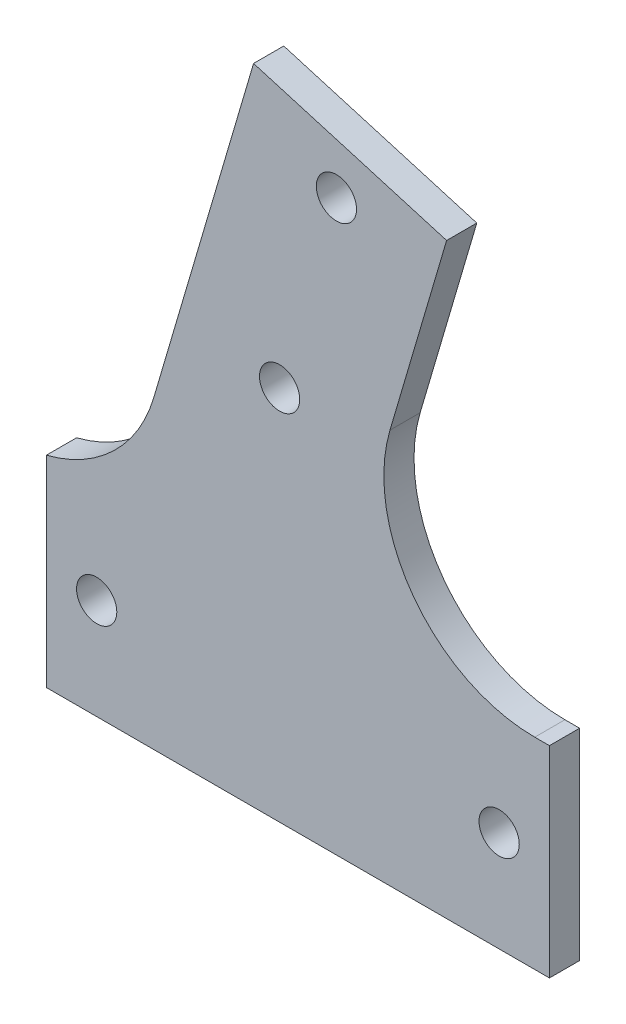
SolidWorks part; units mm, degrees
ref_plane "前视基准面" through (0, 0, 0) normal (0, 0, 1) x (1, 0, 0)
ref_plane "上视基准面" through (0, 0, 0) normal (0, 1, 0) x (1, 0, 0)
ref_plane "右视基准面" through (0, 0, 0) normal (1, 0, 0) x (0, 0, -1)
sketch "草图1" plane through (0, 0, 0) normal (0, 0, 1) x (1, 0, 0)
  line L0 (-1000, 0) -> (49000, 0) construction
  line L1 (-25, 10) -> (25, 10)
  line L2 (-25, 10) -> (-25, -10)
  line L3 (-25, -10) -> (25, -10)
  line L4 (25, 10) -> (25, -10)
  line L5 (-25, 10) -> (25, -10) construction
  line L6 (-25, -10) -> (25, 10) construction
  circle A0 centre (20, 0) radius 2
  circle A1 centre (-20, 0) radius 2
  point P0 (0, 0)
  dimension "D3" = 4
  dimension "D4" = 4
  dimension "D6" = 20
  dimension "D1" = 20
  dimension "D2" = 50
  dimension "D5" = 20
extrude "凸台-拉伸1" add sketch "草图1" along normal blind 3
sketch "草图2" plane through (0, 0, 0) normal (0, 0, -1) x (-1, 0, 0)
  line L0 (-4.9551, 14.9673) -> (-115, 389.1198) construction
  line L1 (14.2322, 20.6106) -> (-95.8127, 394.7631) construction
  line L2 (-3.4942, 10) -> (-14.7808, 48.3746)
  line L3 (17.3529, 10) -> (4.4065, 54.0179)
  line L4 (-25, 10) -> (25, 10) construction
  line L5 (-14.7808, 48.3746) -> (4.4065, 54.0179)
  line L6 (17.3529, 10) -> (-3.4942, 10)
  circle A0 centre (-3.8265, 46.5699) radius 2 construction
  circle A1 centre (1.8169, 27.3826) radius 2 construction
  circle A2 centre (-3.8265, 46.5699) radius 2
  circle A3 centre (1.8169, 27.3826) radius 2
  dimension "D1" = 40
extrude "凸台-拉伸2" add sketch "草图2" against normal blind 3
fillet "圆角1" radius 15 2 edges at (-17.3529, 10, 1.5) (3.4942, 10, 1.5)
